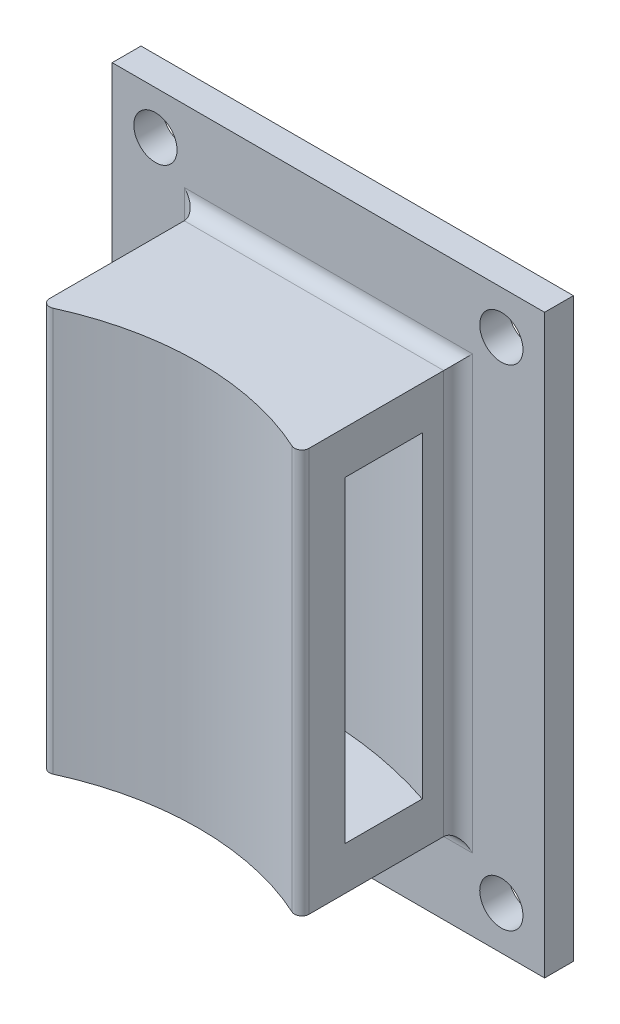
SolidWorks part; units mm, degrees
ref_plane "前视基准面" through (0, 0, 0) normal (0, 0, 1) x (1, 0, 0)
ref_plane "上视基准面" through (0, 0, 0) normal (0, 1, 0) x (1, 0, 0)
ref_plane "右视基准面" through (0, 0, 0) normal (1, 0, 0) x (0, 0, -1)
sketch "草图1" plane through (0, 0, 0) normal (0, 1, 0) x (1, 0, 0)
  line L0 (-9, 31) -> (-9, 26.5141)
  line L1 (0, -1000) -> (0, 49000) construction
  line L2 (9, 31) -> (9, 26.5141)
  line L3 (-9, 31) -> (9, 31)
  line L4 (-9, 21.166) -> (-9, 17.8606)
  line L5 (9, 21.166) -> (9, 17.8606)
  arc A0 (9, 17.8606) -> (-9, 17.8606) centre (0, 0) ccw
  arc A1 (9, 21.166) -> (-9, 21.166) centre (0, 0) ccw
  arc A2 (9, 26.5141) -> (-9, 26.5141) centre (0, 0) ccw
  circle A3 centre (0, 0) radius 28 construction
  circle A4 centre (0, 0) radius 23 construction
  circle A5 centre (0, 0) radius 20 construction
  dimension "D1" = 40
  dimension "D4" = 18
  dimension "D5" = 31
  dimension "D2" = 3
  dimension "D3" = 5
extrude "凸台-拉伸1" add sketch "草图1" along normal mid plane 22
sketch "草图2" plane through (0, 11, 0) normal (0, 1, 0) x (1, 0, 0)
  line L0 (-9, 31) -> (-9, 17.8606)
  line L2 (9, 17.8606) -> (9, 21.166)
  line L3 (9, 31) -> (-9, 31)
  line L4 (-9, 31) -> (-9, 26.5141)
  line L5 (9, 26.5141) -> (9, 31)
  line L6 (9, 31) -> (-9, 31)
  line L9 (-9, 21.166) -> (-9, 17.8606)
  line L12 (9, 17.8606) -> (9, 31)
  arc A1 (9, 26.5141) -> (-9, 26.5141) centre (0, 0) ccw
  arc A4 (9, 17.8606) -> (-9, 17.8606) centre (0, 0) ccw
  arc A5 (9, 21.166) -> (-9, 21.166) centre (0, 0) ccw
  arc A6 (9, 17.8606) -> (-9, 17.8606) centre (0, 0) ccw
  dimension "D1" = 0
  dimension "D2" = 0
extrude "凸台-拉伸2" add sketch "草图2" along normal blind 3
mirror "镜向1" about plane through (0, 0, 0) normal (0, 1, 0) of "凸台-拉伸2"
sketch "草图5" plane through (0, 0, -31) normal (0, 0, -1) x (-1, 0, 0)
  line L8 (-9, 14) -> (-9, -14)
  line L9 (-9, -14) -> (9, -14)
  line L10 (9, -14) -> (9, 14)
  line L11 (9, 14) -> (-9, 14)
  line L12 (-9, 14) -> (-9, -14)
  line L13 (-9, -14) -> (9, -14)
  line L14 (9, -14) -> (9, 14)
  line L15 (9, 14) -> (-9, 14)
  line L20 (-15, 20) -> (-15, -20)
  line L21 (-15, -20) -> (15, -20)
  line L22 (15, -20) -> (15, 20)
  line L23 (15, 20) -> (-15, 20)
  line L24 (-15, 20) -> (-15, -20)
  line L25 (-15, -20) -> (15, -20)
  line L26 (15, -20) -> (15, 20)
  line L27 (15, 20) -> (-15, 20)
  dimension "D1" = 0
  dimension "D2" = 6
extrude "凸台-拉伸3" add sketch "草图5" against normal blind 2
sketch "草图6" plane through (0, 0, -29) normal (0, 0, 1) x (1, 0, 0)
  line L0 (15, 20) -> (15, -20) construction
  line L1 (-15, 20) -> (15, 20) construction
  line L2 (0, 20) -> (0, -20) construction
  line L3 (15, -20) -> (-15, -20) construction
  line L4 (-15, 0) -> (15, 0) construction
  line L5 (-15, -20) -> (-15, 20) construction
  circle A0 centre (12, 17) radius 1.5
  circle A1 centre (-12, 17) radius 1.5
  circle A2 centre (12, -17) radius 1.5
  circle A3 centre (-12, -17) radius 1.5
  dimension "D1" = 3
  dimension "D2" = 24
  dimension "D3" = 34
extrude "切除-拉伸1" cut sketch "草图6" against normal through all
fillet "圆角1" radius 1 4 edges at (9, 0, -29) (0, 14, -29) (-9, 0, -29) (0, -14, -29)
fillet "圆角2" radius 0.5 2 edges at (9, 0, -17.8606) (-9, 0, -17.8606)
